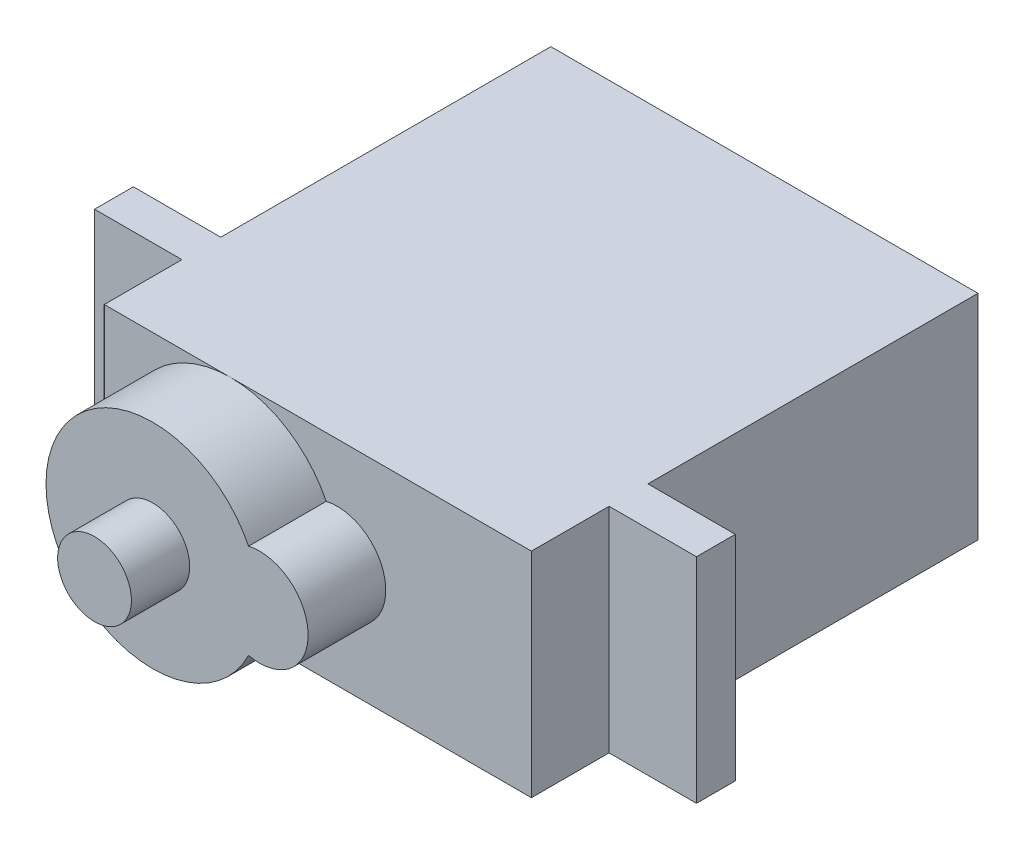
SolidWorks part; units mm, degrees
ref_plane "Front Plane" through (0, 0, 0) normal (0, 0, 1) x (1, 0, 0)
ref_plane "Top Plane" through (0, 0, 0) normal (0, 1, 0) x (1, 0, 0)
ref_plane "Right Plane" through (0, 0, 0) normal (1, 0, 0) x (0, 0, -1)
sketch "Sketch2" plane through (0, 0, 0) normal (0, 0, 1) x (1, 0, 0)
  line L0 (-15.5, 0) -> (15.5, 0) construction
  line L1 (-15.5, 5.5) -> (15.5, 5.5)
  line L2 (-15.5, 5.5) -> (-15.5, -5.5)
  line L3 (-15.5, -5.5) -> (15.5, -5.5)
  line L4 (15.5, 5.5) -> (15.5, -5.5)
  line L5 (-15.5, 5.5) -> (15.5, -5.5) construction
  line L6 (-15.5, -5.5) -> (15.5, 5.5) construction
  circle A0 centre (-4.5, 0) radius 1.9
  point P0 (0, 0)
  dimension "D3" = 3.8
  dimension "D1" = 31
  dimension "D2" = 11
  dimension "D4" = 11
extrude "Boss-Extrude1" add sketch "Sketch2" along normal blind 23
extrude "Boss-Extrude2" add sketch "Sketch2<2>" along normal blind 30 contours A0 region at (-4.5, 0, 0)
sketch "Sketch2<2>" plane through (0, 0, 0) normal (0, 0, 1) x (1, 0, 0) same geometry as "Sketch2"
sketch "Sketch3" plane through (0, 0, 23) normal (0, 0, 1) x (1, 0, 0)
  line L0 (-15.5, -5.5) -> (15.5, -5.5) construction
  line L1 (-11, 5.5) -> (11, 5.5)
  line L2 (-11, 5.5) -> (-11, -5.5)
  line L3 (-11, -5.5) -> (11, -5.5)
  line L4 (11, 5.5) -> (11, -5.5)
  line L5 (-11, 5.5) -> (11, -5.5) construction
  line L6 (-11, -5.5) -> (11, 5.5) construction
  line L8 (-11, 5.5) -> (-15.5, 5.5)
  line L9 (-11, 5.5) -> (-11, -5.5)
  line L10 (-11, -5.5) -> (-15.5, -5.5)
  line L11 (-15.5, 5.5) -> (-15.5, -5.5)
  line L12 (11, 5.5) -> (15.5, 5.5)
  line L13 (11, 5.5) -> (11, -5.5)
  line L14 (11, -5.5) -> (15.5, -5.5)
  line L15 (15.5, 5.5) -> (15.5, -5.5)
  point P0 (0, 0)
  line M2 (15.5, -5.5) -> (15.5, 5.5)
  line M3 (15.5, 5.5) -> (-15.5, 5.5)
  line M4 (-15.5, 5.5) -> (-15.5, -5.5)
  line M5 (-15.5, -5.5) -> (15.5, -5.5)
  dimension "D1" = 22
extrude "Cut-Extrude1" cut sketch "Sketch3" against normal blind 4 contours L2 M3 M4 M5 | L4 M3 M5 M2 region at (-13.25, 0, 23) region at (13.25, 0, 23)
extrude "Cut-Extrude2" cut sketch "Sketch3<5>" against normal through all from offset 6 contours L2 M3 M4 M5 | L4 M3 M5 M2 region at (-13.25, 0, 23) region at (13.25, 0, 23) offset against normal yes
sketch "Sketch3<5>" plane through (0, 0, 23) normal (0, 0, 1) x (1, 0, 0) same geometry as "Sketch3"
sketch "Sketch4" plane through (0, 0, 23) normal (0, 0, 1) x (1, 0, 0)
  line L0 (-11, 0) -> (11, 0) construction
  line L1 (-11, 5.5) -> (-11, -5.5) construction
  line L2 (11, 5.5) -> (11, -5.5) construction
  circle A0 centre (-4.5, 0) radius 5.5
  arc A1 (0.4318, -2.4346) -> (0.4318, 2.4346) centre (1, 0) ccw
  circle M1 centre (-4.5, 0) radius 1.9
  dimension "D1" = 11
  dimension "D2" = 5
  dimension "D3" = 12
extrude "Boss-Extrude3" add sketch "Sketch4" along normal blind 4 contours A0 L0 M1 | L0 A0 M1 | L0 M1 | L0 M1 | L0 A0 A1 | A0 L0 A1 region at (-4.5, 2.5413, 23) region at (-4.5, -0.8064, 23) region at (-4.5, 0.8064, 23) region at (-4.5, -2.5413, 23) region at (1.9521, 1.1321, 23) region at (1.9521, -1.1321, 23)
